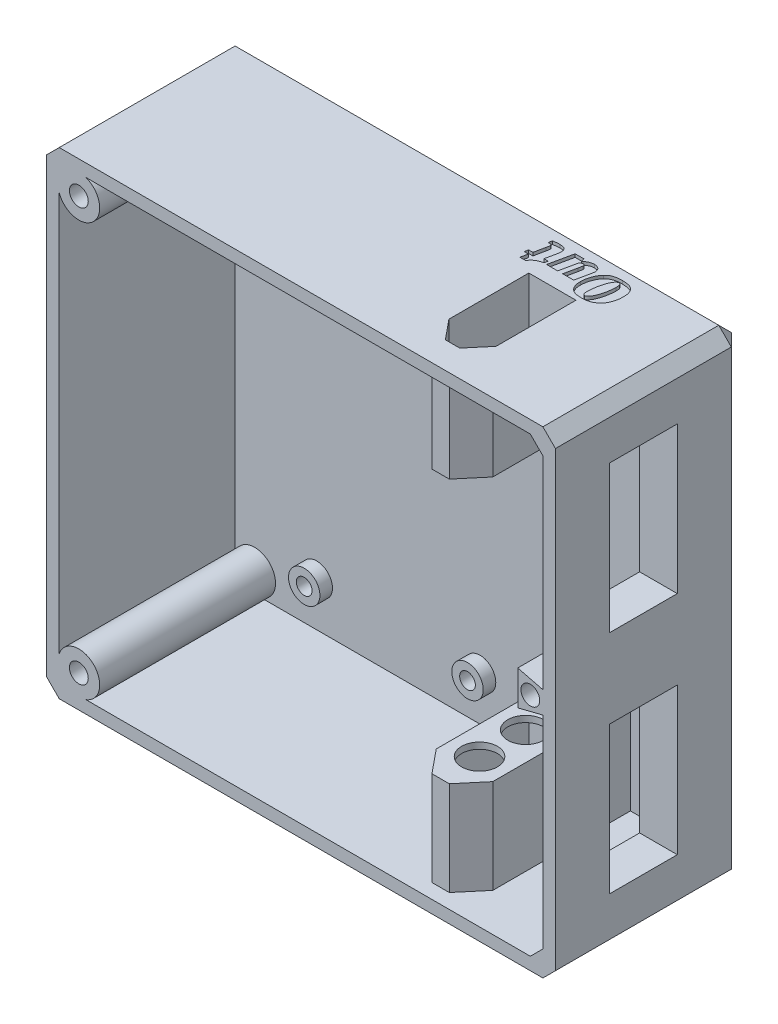
SolidWorks part; units mm, degrees
ref_plane "Front Plane" through (0, 0, 0) normal (0, 0, 1) x (1, 0, 0)
ref_plane "Top Plane" through (0, 0, 0) normal (0, 1, 0) x (1, 0, 0)
ref_plane "Right Plane" through (0, 0, 0) normal (1, 0, 0) x (0, 0, -1)
sketch "Sketch1" plane through (0, 0, 0) normal (0, 0, 1) x (1, 0, 0)
  line L0 (-40, 35) -> (-41, 35) construction
  line L1 (-2, -29) -> (-28, -29) construction
  line L2 (-2, -29) -> (-2, 29) construction
  line L3 (-2, 29) -> (-28, 29) construction
  line L4 (-28, -29) -> (-28, 29) construction
  line L5 (-2, -29) -> (-28, 29) construction
  line L6 (-2, 29) -> (-28, -29) construction
  line L7 (35, -35) -> (-40, -35)
  line L8 (35, -35) -> (35, 35)
  line L9 (35, 35) -> (-40, 35)
  line L10 (-40, -35) -> (-40, 35)
  line L11 (35, -35) -> (-40, 35) construction
  line L12 (35, 35) -> (-40, -35) construction
  line L13 (-40, 35) -> (-40, 36) construction
  line L14 (-41, 35) -> (-5, 35) construction
  line L15 (36, -36) -> (-41, -36)
  line L16 (36, -36) -> (36, 36)
  line L17 (36, 36) -> (-41, 36)
  line L18 (-41, -36) -> (-41, 36)
  line L19 (36, -36) -> (-41, 36) construction
  line L20 (36, 36) -> (-41, -36) construction
  line L21 (-40, 36) -> (-40, 38) construction
  line L22 (0, 0) -> (-15, 0)
  line L23 (38, -38) -> (-43, -38)
  line L24 (38, -38) -> (38, 38)
  line L25 (38, 38) -> (-43, 38)
  line L26 (-43, -38) -> (-43, 38)
  line L27 (38, -38) -> (-43, 38) construction
  line L28 (38, 38) -> (-43, -38) construction
  circle A0 centre (-2, 29) radius 1.25
  circle A1 centre (-28, 29) radius 1.25
  circle A2 centre (-2, -29) radius 1.25
  circle A3 centre (-28, -29) radius 1.25
  point P0 (-15, 0)
  point P10 (-15, 0)
  point P15 (-15, 0)
  point P18 (-15, 0)
  point P24 (-15, 0)
  dimension "D3" = 1
  dimension "D1" = 58
  dimension "D2" = 26
  dimension "D4" = 1
  dimension "D5" = 75
  dimension "D6" = 70
  dimension "D7" = 72
  dimension "D8" = 76
  dimension "D9" = 15
extrude "Boss-Extrude1" add sketch "Sketch1" along normal blind 30 contours L26 L23 L24 L25 L15 L18 L17 L16 region at (-2.5, -36.8893, 0)
extrude "Boss-Extrude2" add sketch "Sketch1<3>" along normal blind 2 contours L18 L15 L16 L17 L7 L10 L9 L8 | L10 L7 L8 L9 A3 A2 A1 A0 region at (-2.5, -33.9741, 0) region at (-2.5, -35.8946, 0)
sketch "Sketch1<3>" plane through (0, 0, 0) normal (0, 0, 1) x (1, 0, 0) same geometry as "Sketch1"
extrude "Boss-Extrude3" add sketch "Sketch1<4>" along normal blind 2 contours A0 | A1 | A2 | A3 region at (-2, 29, 0) region at (-28, 29, 0) region at (-2, -29, 0) region at (-28, -29, 0)
sketch "Sketch1<4>" plane through (0, 0, 0) normal (0, 0, 1) x (1, 0, 0) same geometry as "Sketch1"
extrude "Cut-Extrude1" cut sketch "Sketch1<5>" along normal blind 1 from offset 1 contours A1 | A0 | A2 | A3 region at (-2, 29, 0) region at (-28, 29, 0) region at (-2, -29, 0) region at (-28, -29, 0)
sketch "Sketch1<5>" plane through (0, 0, 0) normal (0, 0, 1) x (1, 0, 0) same geometry as "Sketch1"
sketch "Sketch2" plane through (0, 0, 2) normal (0, 0, 1) x (1, 0, 0)
  circle A0 centre (-2, 29) radius 2.5
  circle A1 centre (-28, 29) radius 2.5
  circle A2 centre (-2, -29) radius 2.5
  circle A3 centre (-28, -29) radius 2.5
  circle A4 centre (-28, 29) radius 1.25 construction
  circle A5 centre (-28, 29) radius 1.25
  circle A6 centre (-2, 29) radius 1.25 construction
  circle A7 centre (-2, 29) radius 1.25
  circle A8 centre (-2, -29) radius 1.25 construction
  circle A9 centre (-2, -29) radius 1.25
  circle A10 centre (-28, -29) radius 1.25 construction
  circle A11 centre (-28, -29) radius 1.25
extrude "Boss-Extrude4" add sketch "Sketch2" along normal blind 2
chamfer "Chamfer2" distance 2 angle 45 12 edges at (-41, -36, 16) (36, -36, 16) (36, 36, 16) (-41, 36, 16) (-2.5, -38, 0) (38, -38, 15) (38, 0, 0) (38, 38, 15) (-2.5, 38, 0) (-43, 38, 15) (-43, 0, 0) (-43, -38, 15)
sketch "Sketch3" plane through (38, 0, 0) normal (1, 0, 0) x (0, 0, -1)
  line L0 (-30, 0) -> (-2, 0) construction
  line L1 (-21.4, 6.3) -> (-10.6, 6.3)
  line L2 (-21.4, 6.3) -> (-21.4, 29.7)
  line L3 (-21.4, 29.7) -> (-10.6, 29.7)
  line L4 (-10.6, 6.3) -> (-10.6, 29.7)
  line L5 (-21.4, 6.3) -> (-10.6, 29.7) construction
  line L6 (-21.4, 29.7) -> (-10.6, 6.3) construction
  line L7 (-30, -36) -> (-30, 36) construction
  line L8 (-2, -36) -> (-2, 36) construction
  line L9 (-16, 0) -> (-16, 36) construction
  line L10 (-2, 36) -> (-30, 36) construction
  line L11 (-21.4, -29.7) -> (-10.6, -6.3) construction
  line L12 (-21.4, -6.3) -> (-10.6, -29.7) construction
  line L13 (-10.6, -6.3) -> (-10.6, -29.7)
  line L14 (-21.4, -29.7) -> (-10.6, -29.7)
  line L15 (-21.4, -6.3) -> (-21.4, -29.7)
  line L16 (-21.4, -6.3) -> (-10.6, -6.3)
  point P0 (-16, 18)
  point P15 (-16, 18)
  point P20 (-16, -18)
extrude "Cut-Extrude2" cut sketch "Sketch3" against normal up to surface (2 mm away) up to face at (36, 0, 16)
sketch "Sketch4" plane through (36, 0, 0) normal (-1, 0, 0) x (0, 0, 1)
  line L0 (21.4, -6.3) -> (10.6, -29.7)
  line L1 (16, -31.335) -> (16, -4.665)
  line L2 (0, 0) -> (10.6, 0) construction
  line L3 (8.5, -34.25) -> (23.5, -34.25)
  line L4 (8.5, -34.25) -> (8.5, -1.75)
  line L5 (8.5, -1.75) -> (23.5, -1.75)
  line L6 (23.5, -34.25) -> (23.5, -1.75)
  line L7 (8.5, -34.25) -> (23.5, -1.75) construction
  line L8 (8.5, -1.75) -> (23.5, -34.25) construction
  line L9 (8.5, 1.75) -> (23.5, 34.25) construction
  line L10 (8.5, 34.25) -> (23.5, 1.75) construction
  line L11 (23.5, 34.25) -> (23.5, 1.75)
  line L12 (8.5, 1.75) -> (23.5, 1.75)
  line L13 (8.5, 34.25) -> (8.5, 1.75)
  line L14 (8.5, 34.25) -> (23.5, 34.25)
  line L15 (16, 31.335) -> (16, 4.665)
  line L16 (21.4, 6.3) -> (10.6, 29.7)
  circle A0 centre (16, -4.665) radius 1.25
  circle A1 centre (16, -31.335) radius 1.25
  circle A2 centre (16, 31.335) radius 1.25
  circle A3 centre (16, 4.665) radius 1.25
  point P7 (16, -18)
  point P9 (16, -18)
  point P27 (16, 18)
  line M2 (21.4, -29.7) -> (10.6, -29.7)
  line M3 (10.6, -29.7) -> (10.6, -6.3)
  line M4 (10.6, -6.3) -> (21.4, -6.3)
  line M5 (21.4, -6.3) -> (21.4, -29.7)
  line M6 (10.6, 29.7) -> (21.4, 29.7)
  line M7 (21.4, 29.7) -> (21.4, 6.3)
  line M8 (21.4, 6.3) -> (10.6, 6.3)
  line M9 (10.6, 6.3) -> (10.6, 29.7)
  line M11 (2, -34) -> (30, -34)
  line M13 (30, 34) -> (2, 34)
extrude "Boss-Extrude5" add sketch "Sketch4" along normal blind 4 contours L13 L12 L11 A3 A2 M13 M8 M9 M6 M7 | L6 L5 L4 A1 A0 M11 M2 M3 M4 M5 region at (36, -17.875, 8.8557) region at (36, 17.875, 23.1443)
chamfer "Chamfer3" distance 1 distance2 4 6 edges at (32, -34, 16) (32, -17.875, 23.5) (32, -1.75, 16) (32, 34, 16) (32, 1.75, 16) (32, 17.875, 23.5) first distance on face at (32, -18, 16) first distance on face at (32, 4.665, 17.25)
sketch "Sketch5" plane through (0, 0, 2) normal (0, 0, 1) x (1, 0, 0)
  line L0 (-40, 35) -> (-37.8787, 32.8787)
  line L1 (-41, 34) -> (-39, 36) construction
  line L2 (-39, 36) -> (-41, 34) construction
  line L3 (0, 0) -> (-22.5817, 0) construction
  line L4 (34, 2.25) -> (34, -2.25) construction
  line L5 (32, 2.75) -> (36, 1.75) construction
  line L6 (32, -2.75) -> (36, -1.75) construction
  line L7 (36, 1.75) -> (36, -1.75)
  line L8 (36, -1.75) -> (32, -2.75)
  line L9 (32, -2.75) -> (32, 2.75)
  line L10 (32, 2.75) -> (36, 1.75)
  circle A0 centre (-37.8787, 32.8787) radius 1.5
  circle A1 centre (-37.8787, -32.8787) radius 1.5
  circle A2 centre (-37.8787, 32.8787) radius 3.3166
  circle A3 centre (-37.8787, -32.8787) radius 3.3166
  circle A4 centre (34, 0) radius 1.5
  line M5 (-41, 34) -> (-41, -34)
  line M6 (-41, -34) -> (-39, -36)
  line M7 (-39, -36) -> (34, -36)
  line M9 (36, -34) -> (36, 34)
  line M11 (34, 36) -> (-39, 36)
  line M12 (-39, 36) -> (-41, 34)
  dimension "D2" = 3
  dimension "D1" = 90
extrude "Boss-Extrude6" add sketch "Sketch5" along normal up to surface (28 mm away) from vertex contours L10 L9 L8 A4 M9 region at (35.932, 0, 2) up to face at (-2.5, 0, 30) starting at point (32, 2.75, 8.5)
extrude "Boss-Extrude11" add sketch "Sketch5<7>" along normal up to surface (28 mm away) contours A2 A0 M5 M11 M12 | A3 A1 M7 M5 M6 region at (-39.4356, 35.4356, 2) region at (-37.3252, -29.7009, 2) up to face at (-2.5, 0, 30)
sketch "Sketch5<7>" plane through (0, 0, 2) normal (0, 0, 1) x (1, 0, 0) same geometry as "Sketch5"
sketch "Sketch6" plane through (-5.8824, 23.5294, 0) normal (-0.2425, 0.9701, 0) x (0.9701, 0.2425, 0)
  line L4 (39.0482, -22.5) -> (43.1713, -23.5)
  line L5 (43.1713, -23.5) -> (43.1713, -8.5)
  line L6 (43.1713, -8.5) -> (39.0482, -8.5)
  line L7 (39.0482, -8.5) -> (39.0482, -22.5)
  line L8 (39.0482, -22.5) -> (43.1713, -23.5)
  line L9 (43.1713, -23.5) -> (43.1713, -8.5)
  line L10 (43.1713, -8.5) -> (39.0482, -8.5)
  line L11 (39.0482, -8.5) -> (39.0482, -22.5)
  dimension "D1" = 0
extrude "Boss-Extrude12" add sketch "Sketch6" along normal up to surface (2.0616 mm away) up to face at (-1.3787, 36, 16)
sketch "Sketch7" plane through (-5.8824, -23.5294, 0) normal (-0.2425, -0.9701, 0) x (0.9701, -0.2425, 0)
  line L4 (39.0482, 8.5) -> (43.1713, 8.5)
  line L5 (43.1713, 8.5) -> (43.1713, 23.5)
  line L6 (43.1713, 23.5) -> (39.0482, 22.5)
  line L7 (39.0482, 22.5) -> (39.0482, 8.5)
  line L8 (39.0482, 8.5) -> (43.1713, 8.5)
  line L9 (43.1713, 8.5) -> (43.1713, 23.5)
  line L10 (43.1713, 23.5) -> (39.0482, 22.5)
  line L11 (39.0482, 22.5) -> (39.0482, 8.5)
  dimension "D1" = 0
extrude "Boss-Extrude13" add sketch "Sketch7" along normal up to surface (2.0616 mm away) up to face at (-1.3787, -36, 16)
sketch "Sketch11" plane through (0, -38, 0) normal (0, -1, 0) x (1, 0, 0)
  line L0 (17.3936, 25.7693) -> (17.3936, 22.6393) construction
  line L1 (18.5436, 25.7693) -> (16.2436, 25.7693)
  line L2 (21.182, 22.6393) -> (21.182, 9.9193)
  line L3 (21.182, 9.9193) -> (13.682, 9.9193)
  line L4 (13.682, 22.6393) -> (13.682, 9.9193)
  line L7 (17.3936, 22.6393) -> (13.682, 22.6393) construction
  line L8 (13.682, 22.6393) -> (21.182, 22.6393) construction
  line L9 (16.2436, 25.7693) -> (13.682, 22.6393)
  line L10 (18.5436, 25.7693) -> (21.182, 22.6393)
  point P12 (17.3936, 25.7693)
  dimension "D1" = 7.5
  dimension "D2" = 15.85
  dimension "D3" = 3.13
  dimension "D4" = 2.3
extrude "Cut-Extrude3" cut sketch "Sketch11" against normal up to surface (2 mm away) up to face at (15.6232, -36, 15.8309)
sketch "Sketch12" plane through (0, -36, 0) normal (0, 1, 0) x (1, 0, 0)
  line L0 (21.182, -22.6393) -> (21.182, -9.9193) construction
  line L1 (21.182, -22.6393) -> (21.182, -9.9193)
  line L2 (21.182, -9.9193) -> (13.682, -9.9193) construction
  line L3 (21.182, -9.9193) -> (13.682, -9.9193)
  line L4 (13.682, -9.9193) -> (13.682, -22.6393) construction
  line L5 (13.682, -9.9193) -> (13.682, -22.6393)
  line L6 (13.682, -22.6393) -> (16.2436, -25.7693) construction
  line L7 (13.682, -22.6393) -> (16.2436, -25.7693)
  line L8 (16.2436, -25.7693) -> (18.5436, -25.7693) construction
  line L9 (16.2436, -25.7693) -> (18.5436, -25.7693)
  line L10 (18.5436, -25.7693) -> (21.182, -22.6393) construction
  line L11 (18.5436, -25.7693) -> (21.182, -22.6393)
  line L12 (21.932, -23.9113) -> (21.932, -8.6473)
  line L13 (18.7659, -27.6673) -> (21.932, -23.9113)
  line L14 (12.932, -8.6473) -> (12.932, -23.9113)
  line L15 (21.932, -8.6473) -> (12.932, -8.6473)
  line L16 (12.932, -23.9113) -> (16.0059, -27.6673)
  line L17 (16.0059, -27.6673) -> (18.7659, -27.6673)
  line L18 (13.682, -9.9193) -> (21.182, -22.6393) construction
  line L19 (12.932, -8.6473) -> (21.932, -23.9113) construction
extrude "Boss-Extrude14" add sketch "Sketch12" along normal up to surface (14 mm away)
ref_plane "Plane2" through (0, 0, 0) normal (0, 1, 0) x (1, 0, 0)
mirror "Mirror4" about plane through (0, 0, 0) normal (0, 1, 0) of "Cut-Extrude3"
extrude "Boss-Extrude16" add sketch "Sketch12<3>" against normal blind 15 from surface starting at face at (15.6232, 36, 15.8309)
sketch "Sketch12<3>" plane through (0, -36, 0) normal (0, 1, 0) x (1, 0, 0) same geometry as "Sketch12"
sketch "Sketch13" plane through (0, -22, 0) normal (0, 1, 0) x (1, 0, 0)
  line L6 (21.932, -23.9113) -> (21.932, -8.6473)
  line L7 (21.932, -8.6473) -> (12.932, -8.6473)
  line L8 (12.932, -8.6473) -> (12.932, -23.9113)
  line L9 (12.932, -23.9113) -> (16.0059, -27.6673)
  line L10 (16.0059, -27.6673) -> (18.7659, -27.6673)
  line L11 (18.7659, -27.6673) -> (21.932, -23.9113)
  line L12 (21.932, -23.9113) -> (21.932, -8.6473)
  line L13 (21.932, -8.6473) -> (12.932, -8.6473)
  line L14 (12.932, -8.6473) -> (12.932, -23.9113)
  line L15 (12.932, -23.9113) -> (16.0059, -27.6673)
  line L16 (16.0059, -27.6673) -> (18.7659, -27.6673)
  line L17 (18.7659, -27.6673) -> (21.932, -23.9113)
  circle A0 centre (17.432, -14.1693) radius 2.85
  circle A1 centre (17.432, -21.5193) radius 2.85
  dimension "D1" = 0
extrude "Boss-Extrude17" add sketch "Sketch13" along normal blind 1
mirror "Mirror5" about plane through (0, 0, 0) normal (0, 1, 0) of "Boss-Extrude17"
sketch "Sketch14" plane through (0, -38, 0) normal (0, -1, 0) x (1, 0, 0)
  text T0 "IN" font "Racing Sans One" height in points 14
extrude "Cut-Extrude4" cut sketch "Sketch14" against normal blind 0.5
sketch "Sketch15" plane through (0, 38, 0) normal (0, 1, 0) x (1, 0, 0)
  line L0 (24.8003, -3.5791) -> (6.1897, -3.5791) construction
  text T0 "Out" font "Racing Sans One" height in points 16
  point P3 (23.4916, -4.8254)
  point P4 (24.8003, -2.8936)
extrude "Cut-Extrude5" cut sketch "Sketch15" against normal blind 0.5
sketch "Sketch16" plane through (0, 0, 8.6473) normal (0, 0, -1) x (-1, 0, 0)
  line L0 (0, 0) -> (-15.7275, 0) construction
  line L1 (-21.932, 36) -> (-12.932, 36)
  line L2 (-21.932, 21) -> (-21.932, 36)
  line L3 (-12.932, 21) -> (-21.932, 21)
  line L4 (-12.932, 36) -> (-12.932, 21)
  line L5 (-12.932, -36) -> (-12.932, -21)
  line L6 (-12.932, -21) -> (-21.932, -21)
  line L7 (-21.932, -21) -> (-21.932, -36)
  line L8 (-21.932, -36) -> (-12.932, -36)
  line L9 (-12.932, -36) -> (-12.932, -21)
  line L10 (-12.932, -21) -> (-21.932, -21)
  line L11 (-21.932, -21) -> (-21.932, -36)
  line L12 (-21.932, -36) -> (-12.932, -36)
  dimension "D1" = 0
extrude "Boss-Extrude18" add sketch "Sketch16" along normal up to surface (6.6473 mm away) up to face at (-25.5, -29, 2)
